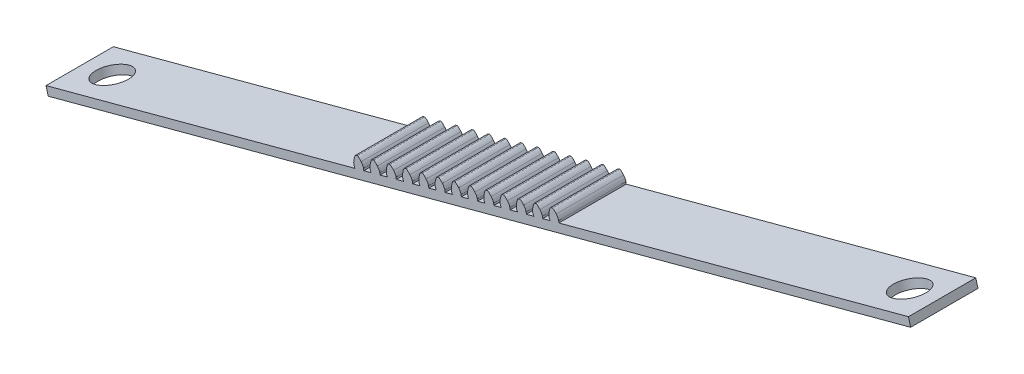
SolidWorks part; units mm, degrees
ref_plane "Front" through (0, 0, 0) normal (0, 0, 1) x (1, 0, 0)
ref_plane "Top" through (0, 0, 0) normal (0, 1, 0) x (1, 0, 0)
ref_plane "Right" through (0, 0, 0) normal (1, 0, 0) x (0, 0, -1)
sketch "Sketch1" plane through (0, 0, 0) normal (0, 0, 1) x (1, 0, 0)
  line L4 (134.3507, -1.879) -> (134.3507, 1.296)
  line L6 (-13.353, 5.1734) -> (-16.689, 4.2795)
  line L9 (-16.689, 4.2795) -> (-15.8673, 1.2127)
  line L10 (-15.8673, 1.2127) -> (202.1663, 59.6346)
  line L12 (201.3446, 62.7014) -> (-13.353, 5.1734)
  line L40 (44.9648, 25.1193) -> (45.506, 25.2643)
  line L41 (44.6473, 20.7145) -> (44.3481, 21.3797)
  line L42 (47.9833, 21.6084) -> (47.9098, 22.3341)
  line L43 (51.0984, 26.7628) -> (51.6396, 26.9078)
  line L44 (50.7809, 22.358) -> (50.4817, 23.0232)
  line L45 (54.117, 23.2519) -> (54.0435, 23.9776)
  line L46 (57.232, 28.4063) -> (57.7732, 28.5513)
  line L47 (56.9145, 24.0015) -> (56.6153, 24.6667)
  line L48 (60.2506, 24.8954) -> (60.1771, 25.6211)
  line L49 (63.3656, 30.0498) -> (63.9069, 30.1948)
  line L50 (63.0481, 25.645) -> (62.749, 26.3102)
  line L51 (66.3842, 26.5389) -> (66.3107, 27.2646)
  line L52 (69.4993, 31.6933) -> (70.0405, 31.8383)
  line L53 (69.1818, 27.2885) -> (68.8826, 27.9537)
  line L54 (72.5178, 28.1824) -> (72.4444, 28.9081)
  line L55 (75.6329, 33.3368) -> (76.1741, 33.4818)
  line L56 (75.3154, 28.932) -> (75.0162, 29.5972)
  line L57 (78.6515, 29.8259) -> (78.578, 30.5516)
  line L58 (81.7665, 34.9803) -> (82.3078, 35.1253)
  line L59 (81.449, 30.5755) -> (81.1498, 31.2407)
  line L60 (84.7851, 31.4694) -> (84.7116, 32.1951)
  line L61 (87.9002, 36.6238) -> (88.4414, 36.7688)
  line L62 (87.5827, 32.219) -> (87.2835, 32.8842)
  line L63 (90.9187, 33.1129) -> (90.8452, 33.8386)
  line L64 (94.0338, 38.2673) -> (94.575, 38.4123)
  line L65 (93.7163, 33.8625) -> (93.4171, 34.5277)
  line L66 (97.0524, 34.7564) -> (96.9789, 35.4821)
  line L67 (100.1674, 39.9108) -> (100.7087, 40.0558)
  line L68 (99.8499, 35.506) -> (99.5507, 36.1712)
  line L69 (103.186, 36.3999) -> (103.1125, 37.1256)
  line L70 (106.301, 41.5543) -> (106.8423, 41.6993)
  line L71 (105.9836, 37.1495) -> (105.6844, 37.8147)
  line L72 (109.3196, 38.0434) -> (109.2461, 38.7691)
  line L73 (112.4347, 43.1978) -> (112.9759, 43.3428)
  line L74 (112.1172, 38.793) -> (111.818, 39.4582)
  line L75 (115.4533, 39.6869) -> (115.3798, 40.4126)
  line L76 (118.5683, 44.8413) -> (119.1095, 44.9863)
  line L77 (118.2508, 40.4365) -> (117.9516, 41.1017)
  line L78 (121.5869, 41.3304) -> (121.5134, 42.0561)
  line L88 (201.3446, 62.7014) -> (202.1663, 59.6346)
  spline S40 degree 2 poles (44.3481, 21.3797) (44.0855, 22.3412) (44.2843, 23.3263) knots 0 0 0 1 1 1
  spline S41 degree 3 poles (44.2843, 23.3263) (44.3692, 23.8195) (44.536, 24.4774) (44.7859, 25.0639) (44.9648, 25.1193) knots 0 0 0 0 0.774836 1 1 1 1
  spline S42 degree 3 poles (46.9918, 24.0518) (46.6716, 24.4365) (46.1982, 24.9228) (45.6885, 25.3057) (45.506, 25.2643) knots 0 0 0 0 0.774836 1 1 1 1
  spline S43 degree 2 poles (47.9098, 22.3341) (47.6565, 23.298) (46.9918, 24.0518) knots 0 0 0 1 1 1
  spline S44 degree 2 poles (50.4817, 23.0232) (50.2192, 23.9847) (50.4179, 24.9698) knots 0 0 0 1 1 1
  spline S45 degree 3 poles (50.4179, 24.9698) (50.5028, 25.463) (50.6696, 26.1209) (50.9196, 26.7074) (51.0984, 26.7628) knots 0 0 0 0 0.774836 1 1 1 1
  spline S46 degree 3 poles (53.1254, 25.6953) (52.8053, 26.08) (52.3318, 26.5663) (51.8222, 26.9492) (51.6396, 26.9078) knots 0 0 0 0 0.774836 1 1 1 1
  spline S47 degree 2 poles (54.0435, 23.9776) (53.7901, 24.9415) (53.1254, 25.6953) knots 0 0 0 1 1 1
  spline S48 degree 2 poles (56.6153, 24.6667) (56.3528, 25.6282) (56.5515, 26.6133) knots 0 0 0 1 1 1
  spline S49 degree 3 poles (56.5515, 26.6133) (56.6364, 27.1065) (56.8033, 27.7644) (57.0532, 28.3509) (57.232, 28.4063) knots 0 0 0 0 0.774836 1 1 1 1
  spline S50 degree 3 poles (59.259, 27.3388) (58.9389, 27.7235) (58.4655, 28.2098) (57.9558, 28.5927) (57.7732, 28.5513) knots 0 0 0 0 0.774836 1 1 1 1
  spline S51 degree 2 poles (60.1771, 25.6211) (59.9237, 26.585) (59.259, 27.3388) knots 0 0 0 1 1 1
  spline S52 degree 2 poles (62.749, 26.3102) (62.4864, 27.2717) (62.6852, 28.2568) knots 0 0 0 1 1 1
  spline S53 degree 3 poles (62.6852, 28.2568) (62.7701, 28.75) (62.9369, 29.4079) (63.1868, 29.9944) (63.3656, 30.0498) knots 0 0 0 0 0.774836 1 1 1 1
  spline S54 degree 3 poles (65.3927, 28.9823) (65.0725, 29.367) (64.5991, 29.8533) (64.0894, 30.2362) (63.9069, 30.1948) knots 0 0 0 0 0.774836 1 1 1 1
  spline S55 degree 2 poles (66.3107, 27.2646) (66.0573, 28.2285) (65.3927, 28.9823) knots 0 0 0 1 1 1
  spline S56 degree 2 poles (68.8826, 27.9537) (68.62, 28.9152) (68.8188, 29.9003) knots 0 0 0 1 1 1
  spline S57 degree 3 poles (68.8188, 29.9003) (68.9037, 30.3935) (69.0705, 31.0514) (69.3205, 31.6379) (69.4993, 31.6933) knots 0 0 0 0 0.774836 1 1 1 1
  spline S58 degree 3 poles (71.5263, 30.6258) (71.2062, 31.0105) (70.7327, 31.4968) (70.2231, 31.8797) (70.0405, 31.8383) knots 0 0 0 0 0.774836 1 1 1 1
  spline S59 degree 2 poles (72.4444, 28.9081) (72.191, 29.872) (71.5263, 30.6258) knots 0 0 0 1 1 1
  spline S60 degree 2 poles (75.0162, 29.5972) (74.7537, 30.5587) (74.9524, 31.5438) knots 0 0 0 1 1 1
  spline S61 degree 3 poles (74.9524, 31.5438) (75.0373, 32.037) (75.2042, 32.6949) (75.4541, 33.2814) (75.6329, 33.3368) knots 0 0 0 0 0.774836 1 1 1 1
  spline S62 degree 3 poles (77.6599, 32.2693) (77.3398, 32.654) (76.8663, 33.1403) (76.3567, 33.5232) (76.1741, 33.4818) knots 0 0 0 0 0.774836 1 1 1 1
  spline S63 degree 2 poles (78.578, 30.5516) (78.3246, 31.5155) (77.6599, 32.2693) knots 0 0 0 1 1 1
  spline S64 degree 2 poles (81.1498, 31.2407) (80.8873, 32.2022) (81.086, 33.1873) knots 0 0 0 1 1 1
  spline S65 degree 3 poles (81.086, 33.1873) (81.1709, 33.6805) (81.3378, 34.3384) (81.5877, 34.9249) (81.7665, 34.9803) knots 0 0 0 0 0.774836 1 1 1 1
  spline S66 degree 3 poles (83.7935, 33.9128) (83.4734, 34.2975) (83, 34.7838) (82.4903, 35.1667) (82.3078, 35.1253) knots 0 0 0 0 0.774836 1 1 1 1
  spline S67 degree 2 poles (84.7116, 32.1951) (84.4582, 33.159) (83.7935, 33.9128) knots 0 0 0 1 1 1
  spline S68 degree 2 poles (87.2835, 32.8842) (87.0209, 33.8457) (87.2197, 34.8309) knots 0 0 0 1 1 1
  spline S69 degree 3 poles (87.2197, 34.8309) (87.3046, 35.324) (87.4714, 35.9819) (87.7213, 36.5684) (87.9002, 36.6238) knots 0 0 0 0 0.774836 1 1 1 1
  spline S70 degree 3 poles (89.9272, 35.5563) (89.607, 35.941) (89.1336, 36.4273) (88.6239, 36.8102) (88.4414, 36.7688) knots 0 0 0 0 0.774836 1 1 1 1
  spline S71 degree 2 poles (90.8452, 33.8386) (90.5919, 34.8025) (89.9272, 35.5563) knots 0 0 0 1 1 1
  spline S72 degree 2 poles (93.4171, 34.5277) (93.1546, 35.4892) (93.3533, 36.4744) knots 0 0 0 1 1 1
  spline S73 degree 3 poles (93.3533, 36.4744) (93.4382, 36.9675) (93.6051, 37.6254) (93.855, 38.2119) (94.0338, 38.2673) knots 0 0 0 0 0.774836 1 1 1 1
  spline S74 degree 3 poles (96.0608, 37.1998) (95.7407, 37.5845) (95.2672, 38.0708) (94.7576, 38.4537) (94.575, 38.4123) knots 0 0 0 0 0.774836 1 1 1 1
  spline S75 degree 2 poles (96.9789, 35.4821) (96.7255, 36.446) (96.0608, 37.1998) knots 0 0 0 1 1 1
  spline S76 degree 2 poles (99.5507, 36.1712) (99.2882, 37.1327) (99.4869, 38.1179) knots 0 0 0 1 1 1
  spline S77 degree 3 poles (99.4869, 38.1179) (99.5718, 38.611) (99.7387, 39.2689) (99.9886, 39.8554) (100.1674, 39.9108) knots 0 0 0 0 0.774836 1 1 1 1
  spline S78 degree 3 poles (102.1944, 38.8433) (101.8743, 39.228) (101.4009, 39.7143) (100.8912, 40.0972) (100.7087, 40.0558) knots 0 0 0 0 0.774836 1 1 1 1
  spline S79 degree 2 poles (103.1125, 37.1256) (102.8591, 38.0895) (102.1944, 38.8433) knots 0 0 0 1 1 1
  spline S80 degree 2 poles (105.6844, 37.8147) (105.4218, 38.7762) (105.6206, 39.7614) knots 0 0 0 1 1 1
  spline S81 degree 3 poles (105.6206, 39.7614) (105.7055, 40.2546) (105.8723, 40.9124) (106.1222, 41.4989) (106.301, 41.5543) knots 0 0 0 0 0.774836 1 1 1 1
  spline S82 degree 3 poles (108.3281, 40.4868) (108.0079, 40.8715) (107.5345, 41.3578) (107.0248, 41.7407) (106.8423, 41.6993) knots 0 0 0 0 0.774836 1 1 1 1
  spline S83 degree 2 poles (109.2461, 38.7691) (108.9928, 39.733) (108.3281, 40.4868) knots 0 0 0 1 1 1
  spline S84 degree 2 poles (111.818, 39.4582) (111.5554, 40.4197) (111.7542, 41.4049) knots 0 0 0 1 1 1
  spline S85 degree 3 poles (111.7542, 41.4049) (111.8391, 41.8981) (112.0059, 42.5559) (112.2559, 43.1424) (112.4347, 43.1978) knots 0 0 0 0 0.774836 1 1 1 1
  spline S86 degree 3 poles (114.4617, 42.1303) (114.1416, 42.515) (113.6681, 43.0013) (113.1585, 43.3842) (112.9759, 43.3428) knots 0 0 0 0 0.774836 1 1 1 1
  spline S87 degree 2 poles (115.3798, 40.4126) (115.1264, 41.3765) (114.4617, 42.1303) knots 0 0 0 1 1 1
  spline S88 degree 2 poles (117.9516, 41.1017) (117.6891, 42.0632) (117.8878, 43.0484) knots 0 0 0 1 1 1
  spline S89 degree 3 poles (117.8878, 43.0484) (117.9727, 43.5416) (118.1396, 44.1994) (118.3895, 44.7859) (118.5683, 44.8413) knots 0 0 0 0 0.774836 1 1 1 1
  spline S90 degree 3 poles (120.5953, 43.7738) (120.2752, 44.1585) (119.8018, 44.6448) (119.2921, 45.0277) (119.1095, 44.9863) knots 0 0 0 0 0.774836 1 1 1 1
  spline S91 degree 2 poles (121.5134, 42.0561) (121.26, 43.02) (120.5953, 43.7738) knots 0 0 0 1 1 1
  dimension "D3" = 24
  dimension "D4" = 5
  dimension "D5" = 9
extrude "Boss-Extrude1" add sketch "Sketch1" along normal blind 25.4 contours L88 L12 L9 L10 | L12 | L12 | L12 | L12 | L12 | L12 | L12 | L12 | L12 | L42 S43 S42 L40 S41 S40 L41 L12 | L45 S47 S46 L43 S45 S44 L44 L12 | L48 S51 S50 L46 S49 S48 L47 L12 | L51 S55 S54 L49 S53 S52 L50 L12 | L54 S59 S58 L52 S57 S56 L53 L12 | L57 S63 S62 L55 S61 S60 L56 L12 | L60 S67 S66 L58 S65 S64 L59 L12 | L63 S71 S70 L61 S69 S68 L62 L12 | L66 S75 S74 L64 S73 S72 L65 L12 | L69 S79 S78 L67 S77 S76 L68 L12 | L72 S83 S82 L70 S81 S80 L71 L12 | L75 S87 S86 L73 S85 S84 L74 L12 | L78 S91 S90 L76 S89 S88 L77 L12 | L12 | L12 | L12 | L12 | L12 | L12 | L12 | L12 | L12 | L12 | L12 | L12 | L12 region at (92.7387, 31.957, 0) region at (45.8575, 22.8699, 0) region at (51.9911, 24.5134, 0) region at (119.4611, 42.592, 0) region at (58.1248, 26.1569, 0) region at (113.3274, 40.9485, 0) region at (64.2584, 27.8004, 0) region at (107.1938, 39.305, 0) region at (70.392, 29.4439, 0) region at (101.0602, 37.6615, 0) region at (76.5256, 31.0874, 0) region at (94.9265, 36.0179, 0) region at (82.6593, 32.7309, 0) region at (88.7929, 34.3744, 0)
sketch "Sketch2" plane through (-14.5012, -3.8856, 0) normal (-0.9659, -0.2588, 0) x (0, 0, 1)
  line L1 (0, 8.4531) -> (25.4, 8.4531)
  line L2 (0, 8.4531) -> (0, 5.2781)
  line L3 (0, 5.2781) -> (25.4, 5.2781)
  line L4 (25.4, 8.4531) -> (25.4, 5.2781)
extrude "Boss-Extrude2" add sketch "Sketch2" along normal blind 57.15
sketch "Sketch3" plane through (203.5324, 54.5363, 0) normal (0.9659, 0.2588, 0) x (0, 0, -1)
  line L1 (-25.4, 8.4531) -> (0, 8.4531)
  line L2 (-25.4, 8.4531) -> (-25.4, 5.2781)
  line L3 (-25.4, 5.2781) -> (0, 5.2781)
  line L4 (0, 8.4531) -> (0, 5.2781)
extrude "Boss-Extrude3" add sketch "Sketch3" along normal blind 53.975
sketch "Sketch4" plane through (-2.1878, 8.1651, 0) normal (-0.2588, 0.9659, 0) x (0.9659, 0.2588, 0)
  line L0 (-72.1628, -25.4) -> (48.4872, -25.4) construction
  line L1 (-72.1628, -25.4) -> (-72.1628, 0) construction
  circle A0 centre (-59.4628, -12.7) radius 6.35
  dimension "D3" = 12.7
  dimension "D1" = 12.7
  dimension "D2" = 12.7
extrude "Cut-Extrude3" cut sketch "Sketch4" against normal blind 25.4
sketch "Sketch5" plane through (-2.1878, 8.1651, 0) normal (-0.2588, 0.9659, 0) x (0.9659, 0.2588, 0)
  line L0 (264.6872, 0) -> (264.6872, -25.4) construction
  line L2 (264.6872, 0) -> (128.141, 0) construction
  circle A0 centre (251.9872, -12.7) radius 6.35
  dimension "D3" = 12.7
  dimension "D1" = 12.7
  dimension "D2" = 12.7
extrude "Cut-Extrude4" cut sketch "Sketch5" against normal blind 10
